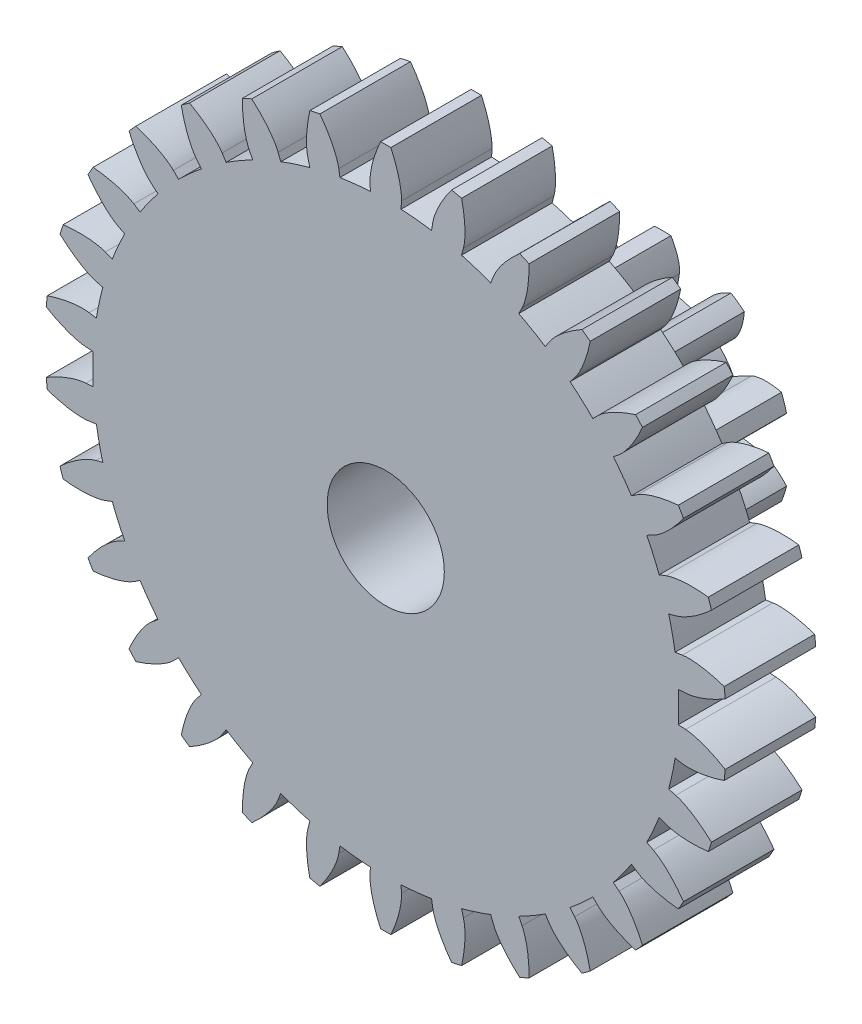
SolidWorks part; units mm, degrees
ref_plane "前视基准面" through (0, 0, 0) normal (0, 0, 1) x (1, 0, 0)
ref_plane "上视基准面" through (0, 0, 0) normal (0, 1, 0) x (1, 0, 0)
ref_plane "右视基准面" through (0, 0, 0) normal (1, 0, 0) x (0, 0, -1)
other "Configuration Table"
sketch "草图1" plane through (0, 0, 0) normal (0, 0, 1) x (1, 0, 0)
  line L0 (0, 0) -> (2, 0) construction
  line L1 (0, 0) -> (1.9754, 0.3129) construction
  line L2 (0, 0) -> (1.8592, 0.2745)
  line L3 (1.9754, 0.3129) -> (1.9754, -0.3129) construction
  line L4 (0, 0) -> (1.8592, -0.2745)
  circle A0 centre (0, 0) radius 2.4
  circle A1 centre (0, 0) radius 2 construction
  circle A2 centre (0, 0) radius 1.5
  circle A3 centre (0, 0) radius 1.8794 construction
  circle A4 centre (0, 0) radius 1.1
  spline S0 degree 4 poles (1.8592, 0.2745) (1.8734, 0.2766) (1.9125, 0.2853) (1.984, 0.3137) (2.0924, 0.375) (2.2192, 0.4755) (2.3619, 0.6263) (2.5009, 0.8263) (2.6204, 1.0654) (2.7124, 1.3385) (2.7699, 1.6207) (2.7951, 1.9074) (2.79, 2.2094) (2.7448, 2.5807) (2.6344, 3.0135) (2.434, 3.4925) (2.132, 3.9838) (1.7625, 4.4264) (1.3371, 4.8149) (0.8651, 5.1458) (0.3578, 5.417) (-0.1795, 5.6274) (-0.6638, 5.7585) (-1.0922, 5.8327) (-1.4439, 5.8705) (-1.7421, 5.8849) (-1.9826, 5.8872) (-2.2673, 5.8741) (-2.452, 5.859) (-2.7142, 5.8298) (-2.9094, 5.7965) (-3.106, 5.7609) (-3.2032, 5.7369) (-3.2666, 5.7231) knots 0 0 0 0 0 0.005604 0.015718 0.02996 0.048734 0.068727 0.096889 0.125051 0.153212 0.181374 0.209535 0.237696 0.271429 0.327752 0.384075 0.440398 0.496721 0.553044 0.609367 0.66569 0.722013 0.778336 0.806497 0.834659 0.86282 0.890982 0.909091 0.931818 0.954545 0.977273 1 1 1 1 1 construction
  spline S1 degree 4 poles (1.8592, 0.2745) (1.8734, 0.2766) (1.9125, 0.2853) (1.984, 0.3137) (2.0924, 0.375) (2.2192, 0.4755) (2.3619, 0.6263) (2.5009, 0.8263) (2.6204, 1.0654) (2.7124, 1.3385) (2.7699, 1.6207) (2.7951, 1.9074) (2.79, 2.2094) (2.7448, 2.5807) (2.6344, 3.0135) (2.434, 3.4925) (2.132, 3.9838) (1.7625, 4.4264) (1.3371, 4.8149) (0.8651, 5.1458) (0.3578, 5.417) (-0.1795, 5.6274) (-0.6638, 5.7585) (-1.0922, 5.8327) (-1.4439, 5.8705) (-1.7421, 5.8849) (-1.9826, 5.8872) (-2.2007, 5.8772) (-2.3078, 5.87) (-2.3497, 5.8667) knots 0 0 0 0 0 0.005604 0.015718 0.02996 0.048734 0.068727 0.096889 0.125051 0.153212 0.181374 0.209535 0.237696 0.271429 0.327752 0.384075 0.440398 0.496721 0.553044 0.609367 0.66569 0.722013 0.778336 0.806497 0.834659 0.86282 0.890982 0.909091 0.909091 0.909091 0.909091 0.909091
  spline S2 degree 4 poles (1.8592, -0.2745) (1.8734, -0.2766) (1.9125, -0.2853) (1.984, -0.3137) (2.0924, -0.375) (2.2192, -0.4755) (2.3619, -0.6263) (2.5009, -0.8263) (2.6204, -1.0654) (2.7124, -1.3385) (2.7699, -1.6207) (2.7951, -1.9074) (2.79, -2.2094) (2.7448, -2.5807) (2.6344, -3.0135) (2.434, -3.4925) (2.132, -3.9838) (1.7625, -4.4264) (1.3371, -4.8149) (0.8651, -5.1458) (0.3578, -5.417) (-0.1795, -5.6274) (-0.6638, -5.7585) (-1.0922, -5.8327) (-1.4439, -5.8705) (-1.7421, -5.8849) (-1.9826, -5.8872) (-2.2673, -5.8741) (-2.452, -5.859) (-2.7142, -5.8298) (-2.9094, -5.7965) (-3.106, -5.7609) (-3.2032, -5.7369) (-3.2666, -5.7231) knots 0 0 0 0 0 0.005604 0.015718 0.02996 0.048734 0.068727 0.096889 0.125051 0.153212 0.181374 0.209535 0.237696 0.271429 0.327752 0.384075 0.440398 0.496721 0.553044 0.609367 0.66569 0.722013 0.778336 0.806497 0.834659 0.86282 0.890982 0.909091 0.931818 0.954545 0.977273 1 1 1 1 1 construction
  spline S3 degree 4 poles (1.8592, -0.2745) (1.8734, -0.2766) (1.9125, -0.2853) (1.984, -0.3137) (2.0924, -0.375) (2.2192, -0.4755) (2.3619, -0.6263) (2.5009, -0.8263) (2.6204, -1.0654) (2.7124, -1.3385) (2.7699, -1.6207) (2.7951, -1.9074) (2.79, -2.2094) (2.7448, -2.5807) (2.6344, -3.0135) (2.434, -3.4925) (2.132, -3.9838) (1.7625, -4.4264) (1.3371, -4.8149) (0.8651, -5.1458) (0.3578, -5.417) (-0.1795, -5.6274) (-0.6638, -5.7585) (-1.0922, -5.8327) (-1.4439, -5.8705) (-1.7421, -5.8849) (-1.9826, -5.8872) (-2.2007, -5.8772) (-2.3078, -5.87) (-2.3497, -5.8667) knots 0 0 0 0 0 0.005604 0.015718 0.02996 0.048734 0.068727 0.096889 0.125051 0.153212 0.181374 0.209535 0.237696 0.271429 0.327752 0.384075 0.440398 0.496721 0.553044 0.609367 0.66569 0.722013 0.778336 0.806497 0.834659 0.86282 0.890982 0.909091 0.909091 0.909091 0.909091 0.909091
  point P15 (1.9754, 0)
  dimension "齿顶圆直径" = 4.8
  dimension "分度圆直径" = 4
  dimension "齿根圆直径" = 3
  dimension "基圆直径" = 3.7588
  dimension "内孔直径" = 2.2
  dimension "渐近线镜像线夹角" = 9
extrude "凸台-拉伸1" add sketch "草图1" along normal blind 3.5 contours A0 | A4
extrude "切除-拉伸1" cut sketch "草图1<3>" along normal through all contours A2 S3 A0 S1 region at (2.016, 0, 0)
sketch "草图1<3>" plane through (0, 0, 0) normal (0, 0, 1) x (1, 0, 0) same geometry as "草图1"
pattern_circular "阵列(圆周)1" count 10 every 36 about axis through (0, 0, 3.5) along (0, 0, 1) of "切除-拉伸1"
sketch "草图2" plane through (0, 0, 3.5) normal (0, 0, 1) x (1, 0, 0)
  line L0 (0, 0) -> (6, 0) construction
  line L1 (0, 0) -> (5.6304, 0.2951)
  line L2 (0, 0) -> (5.6304, -0.2951)
  line L3 (5.6304, 0.2951) -> (5.6304, -0.2951) construction
  circle A0 centre (0, 0) radius 6 construction
  circle A1 centre (0, 0) radius 5.6382 construction
  circle A2 centre (0, 0) radius 5.5
  circle A3 centre (0, 0) radius 6.4
  circle A4 centre (0, 0) radius 1.1
  spline S0 degree 4 poles (5.6304, -0.2951) (5.6519, -0.2962) (5.6945, -0.3005) (5.8129, -0.3229) (6.032, -0.3922) (6.3509, -0.5432) (6.7529, -0.8142) (7.2143, -1.2331) (7.6755, -1.7994) (8.0876, -2.4877) (8.425, -3.2835) (8.6612, -4.1145) (8.8022, -4.9665) (8.8558, -5.871) (8.805, -6.9919) (8.5735, -8.3118) (8.0834, -9.7904) (7.2917, -11.3288) (6.2875, -12.7368) (5.1029, -13.9959) (3.7678, -15.0933) (2.3097, -16.0204) (0.9488, -16.6782) (-0.2638, -17.1311) (-1.2979, -17.4345) (-2.0325, -17.6082) (-2.6669, -17.7296) (-3.2005, -17.8126) (-3.6254, -17.868) (-4.0587, -17.9127) (-4.4801, -17.9466) (-4.8863, -17.9677) (-5.2165, -17.9791) (-5.5938, -17.9835) (-5.838, -17.9825) (-6.2326, -17.9752) (-6.5391, -17.9609) (-6.9112, -17.9398) (-7.2423, -17.9121) (-7.5988, -17.8777) (-7.9363, -17.8368) (-8.2008, -17.8012) (-8.3691, -17.7754) (-8.4565, -17.7619) knots 0 0 0 0 0 0.002802 0.005604 0.015718 0.02996 0.048734 0.068727 0.096889 0.125051 0.153212 0.181374 0.209535 0.237696 0.271429 0.327752 0.384075 0.440398 0.496721 0.553044 0.609367 0.66569 0.722013 0.750174 0.778336 0.806497 0.820578 0.834659 0.84874 0.86282 0.876901 0.890982 0.900036 0.909091 0.920455 0.931818 0.943182 0.954545 0.965909 0.977273 0.988636 1 1 1 1 1 construction
  spline S1 degree 4 poles (5.6304, -0.2951) (5.6519, -0.2962) (5.6945, -0.3005) (5.8129, -0.3229) (6.032, -0.3922) (6.3509, -0.5432) (6.7529, -0.8142) (7.2143, -1.2331) (7.6755, -1.7994) (8.0876, -2.4877) (8.425, -3.2835) (8.6612, -4.1145) (8.8022, -4.9665) (8.8558, -5.871) (8.805, -6.9919) (8.5735, -8.3118) (8.0834, -9.7904) (7.2917, -11.3288) (6.2875, -12.7368) (5.1029, -13.9959) (3.7678, -15.0933) (2.3097, -16.0204) (0.9488, -16.6782) (-0.2638, -17.1311) (-1.2979, -17.4345) (-2.0325, -17.6082) (-2.6669, -17.7296) (-3.2005, -17.8126) (-3.6254, -17.868) (-4.0587, -17.9127) (-4.4801, -17.9466) (-4.8863, -17.9677) (-5.2165, -17.9791) (-5.4954, -17.9824) (-5.6224, -17.9828) (-5.6854, -17.9827) knots 0 0 0 0 0 0.002802 0.005604 0.015718 0.02996 0.048734 0.068727 0.096889 0.125051 0.153212 0.181374 0.209535 0.237696 0.271429 0.327752 0.384075 0.440398 0.496721 0.553044 0.609367 0.66569 0.722013 0.750174 0.778336 0.806497 0.820578 0.834659 0.84874 0.86282 0.876901 0.890982 0.900036 0.909091 0.909091 0.909091 0.909091 0.909091
  spline S2 degree 4 poles (5.6304, 0.2951) (5.6519, 0.2962) (5.6945, 0.3005) (5.8129, 0.3229) (6.032, 0.3922) (6.3509, 0.5432) (6.7529, 0.8142) (7.2143, 1.2331) (7.6755, 1.7994) (8.0876, 2.4877) (8.425, 3.2835) (8.6612, 4.1145) (8.8022, 4.9665) (8.8558, 5.871) (8.805, 6.9919) (8.5735, 8.3118) (8.0834, 9.7904) (7.2917, 11.3288) (6.2875, 12.7368) (5.1029, 13.9959) (3.7678, 15.0933) (2.3097, 16.0204) (0.9488, 16.6782) (-0.2638, 17.1311) (-1.2979, 17.4345) (-2.0325, 17.6082) (-2.6669, 17.7296) (-3.2005, 17.8126) (-3.6254, 17.868) (-4.0587, 17.9127) (-4.4801, 17.9466) (-4.8863, 17.9677) (-5.2165, 17.9791) (-5.5938, 17.9835) (-5.838, 17.9825) (-6.2326, 17.9752) (-6.5391, 17.9609) (-6.9112, 17.9398) (-7.2423, 17.9121) (-7.5988, 17.8777) (-7.9363, 17.8368) (-8.2008, 17.8012) (-8.3691, 17.7754) (-8.4565, 17.7619) knots 0 0 0 0 0 0.002802 0.005604 0.015718 0.02996 0.048734 0.068727 0.096889 0.125051 0.153212 0.181374 0.209535 0.237696 0.271429 0.327752 0.384075 0.440398 0.496721 0.553044 0.609367 0.66569 0.722013 0.750174 0.778336 0.806497 0.820578 0.834659 0.84874 0.86282 0.876901 0.890982 0.900036 0.909091 0.920455 0.931818 0.943182 0.954545 0.965909 0.977273 0.988636 1 1 1 1 1 construction
  spline S3 degree 4 poles (5.6304, 0.2951) (5.6519, 0.2962) (5.6945, 0.3005) (5.8129, 0.3229) (6.032, 0.3922) (6.3509, 0.5432) (6.7529, 0.8142) (7.2143, 1.2331) (7.6755, 1.7994) (8.0876, 2.4877) (8.425, 3.2835) (8.6612, 4.1145) (8.8022, 4.9665) (8.8558, 5.871) (8.805, 6.9919) (8.5735, 8.3118) (8.0834, 9.7904) (7.2917, 11.3288) (6.2875, 12.7368) (5.1029, 13.9959) (3.7678, 15.0933) (2.3097, 16.0204) (0.9488, 16.6782) (-0.2638, 17.1311) (-1.2979, 17.4345) (-2.0325, 17.6082) (-2.6669, 17.7296) (-3.2005, 17.8126) (-3.6254, 17.868) (-4.0587, 17.9127) (-4.4801, 17.9466) (-4.8863, 17.9677) (-5.2165, 17.9791) (-5.4954, 17.9824) (-5.6224, 17.9828) (-5.6854, 17.9827) knots 0 0 0 0 0 0.002802 0.005604 0.015718 0.02996 0.048734 0.068727 0.096889 0.125051 0.153212 0.181374 0.209535 0.237696 0.271429 0.327752 0.384075 0.440398 0.496721 0.553044 0.609367 0.66569 0.722013 0.750174 0.778336 0.806497 0.820578 0.834659 0.84874 0.86282 0.876901 0.890982 0.900036 0.909091 0.909091 0.909091 0.909091 0.909091
  point P16 (5.6304, 0)
  dimension "内孔直径" = 2.2
  dimension "分度圆直径" = 12
  dimension "齿顶圆直径" = 12.8
  dimension "基圆直径" = 11.2763
  dimension "齿根圆直径" = 11
  dimension "渐开线镜像线夹角" = 3
extrude "凸台-拉伸2" add sketch "草图2" along normal blind 1.7 contours A3 | A4
extrude "切除-拉伸3" cut sketch "草图2<3>" along normal through all contours S3 L1 A2 L2 S1 A3 region at (6.002, 0, 3.5)
sketch "草图2<3>" plane through (0, 0, 3.5) normal (0, 0, 1) x (1, 0, 0) same geometry as "草图2"
pattern_circular "阵列(圆周)2" count 30 over 360 about axis through (0, 0, 5.2) along (0, 0, 1) of "切除-拉伸3"
equation "\"m\" = 0.4'模数"
equation "\"z\"= 10'齿数"
equation "\"a\"= 20度'压力角"
equation "\"d\"= \"m\" * \"z\"'分度圆直径"
equation "\"da\"= ( \"z\" + 2 ) * \"m\"'齿顶圆直径"
equation "\"df\"= ( \"z\" - 2.5 ) * \"m\"'齿根圆直径"
equation "\"s\"= 0.5 * PI * \"m\"'分度圆齿厚"
equation "\"r\"= 0.38 * \"m\"'齿根圆角"
equation "\"B\"= 0.3 * \"d\"'齿厚"
equation "\"db\"= \"m\" * \"z\" * cos ( \"a\" )'基圆直径"
equation "\"rb\"= \"db\" / 2'基圆半径"
equation "\"齿顶圆直径@草图1\"= \"da\""
equation "\"分度圆直径@草图1\"= \"d\""
equation "\"齿根圆直径@草图1\"= \"df\""
equation "\"基圆直径@草图1\"= \"db\""
equation "\"渐近线镜像线夹角@草图1\"= 360 / 4 / \"z\""
equation "\"h\" = 3.5mm'齿轮厚度"
equation "\"ir\"= 2.2mm'内孔直径"
equation "\"内孔直径@草图1\"= \"ir\""
equation "\"齿轮厚@凸台-拉伸1\"= \"h\""
equation "\"齿轮夹角@阵列(圆周)1\"= 360 / \"z\""
equation "\"齿数@阵列(圆周)1\"= \"z\""
equation "\"m1\" = 0.4'模数"
equation "\"z1\"= 30'齿数"
equation "\"a1\"= 20度'压力角"
equation "\"d1\"= \"m1\" * \"z1\"'分度圆直径"
equation "\"da1\"= ( \"z1\" + 2 ) * \"m1\"'齿顶圆直径"
equation "\"df1\"= ( \"z1\" - 2.5 ) * \"m1\"'齿根圆直径"
equation "\"s1\"= 0.5 * PI * \"m1\"'分度圆齿厚"
equation "\"r1\"= 0.38 * \"m1\"'齿根圆角"
equation "\"B1\"= 0.3 * \"d1\"'齿厚"
equation "\"db1\"= \"m1\" * \"z1\" * cos ( \"a1\" )'基圆直径"
equation "\"rb1\"= \"db1\" / 2'基圆半径"
equation "\"分度圆直径@草图2\"= \"d1\""
equation "\"齿顶圆直径@草图2\"= \"da1\""
equation "\"基圆直径@草图2\"= \"db1\""
equation "\"齿根圆直径@草图2\"= \"df1\""
equation "\"渐开线镜像线夹角@草图2\"= 360 / 4 / \"z1\""
equation "\"内孔直径@草图2\"= \"ir\""
equation "\"二层齿轮厚@凸台-拉伸2\" = \"h1\""
equation "\"h1\" = 1.7'齿轮厚度"
equation "\"二层齿数@阵列(圆周)2\"= \"z1\""
